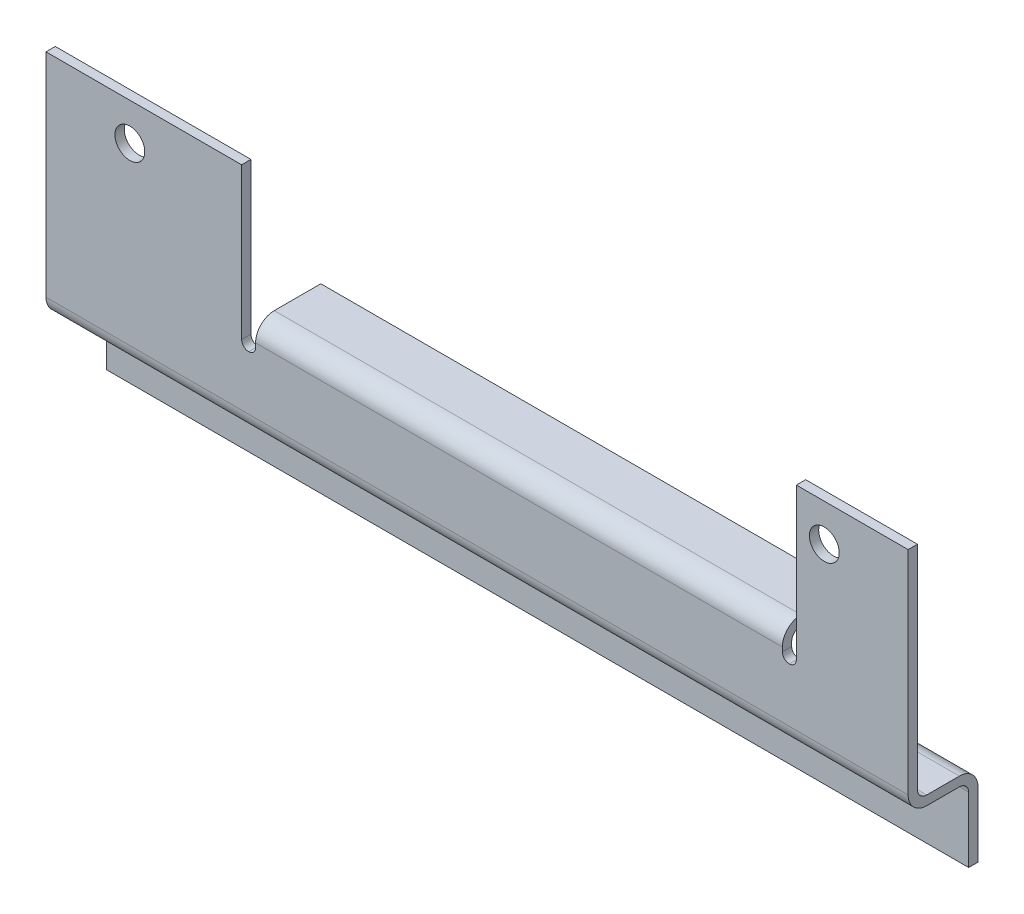
SolidWorks part; units mm, degrees
ref_plane "Face" through (0, 0, 0) normal (0, 0, 1) x (1, 0, 0)
ref_plane "Dessus" through (0, 0, 0) normal (0, 1, 0) x (1, 0, 0)
ref_plane "Droite" through (0, 0, 0) normal (1, 0, 0) x (0, 0, -1)
sketch "Esquisse1" plane through (0, 0, 0) normal (0, 0, 1) x (1, 0, 0)
  line L0 (-46.275, -25.41) -> (-25.275, -25.41)
  line L1 (46.275, -25.41) -> (46.275, -49.22)
  line L3 (-46.275, -25.41) -> (-46.275, -49.22)
  line L5 (34.275, -25.41) -> (34.275, -39.22)
  line L6 (-25.275, -25.41) -> (-25.275, -39.22)
  line L7 (34.275, -25.41) -> (46.275, -25.41)
  line L8 (-25.275, -39.22) -> (34.275, -39.22)
  line L9 (-46.275, -38.22) -> (46.275, -38.22) construction
  line L10 (-46.275, -49.22) -> (46.275, -49.22)
  circle A0 centre (37.275, -29.41) radius 1.75 construction
  circle A1 centre (37.275, -29.41) radius 1.6
  circle A2 centre (-37.275, -29.41) radius 1.6
  dimension "D1" = 4
  dimension "D2" = 12
  dimension "D3" = 21
  dimension "D4" = 1
  dimension "D5" = 10
extrude "Extrusion1" add sketch "Esquisse1" along normal blind 1
sketch "Esquisse2" plane through (0, 0, 1) normal (0, 0, 1) x (1, 0, 0)
  line L1 (-25.275, -39.22) -> (34.275, -39.22)
  line L2 (-25.275, -39.22) -> (-25.275, -40.22)
  line L3 (-25.275, -40.22) -> (34.275, -40.22)
  line L4 (34.275, -39.22) -> (34.275, -40.22)
  dimension "D1" = 1
extrude "Extrusion2" add sketch "Esquisse2" against normal blind 7
sketch "Esquisse3" plane through (0, 0, 1) normal (0, 0, 1) x (1, 0, 0)
  line L1 (-46.275, -49.22) -> (46.275, -49.22)
  line L2 (-46.275, -49.22) -> (-46.275, -50.22)
  line L3 (-46.275, -50.22) -> (46.275, -50.22)
  line L4 (46.275, -49.22) -> (46.275, -50.22)
  dimension "D1" = 1
extrude "Extrusion3" add sketch "Esquisse3" against normal blind 7.5
sketch "Esquisse4" plane through (0, -50.22, 0) normal (0, -1, 0) x (1, 0, 0)
  line L0 (46.275, -6.5) -> (46.275, 1) construction
  line L1 (-46.275, -6.5) -> (46.275, -6.5)
  line L2 (-46.275, -6.5) -> (-46.275, -5.5)
  line L3 (-46.275, -5.5) -> (46.275, -5.5)
  line L4 (46.275, -6.5) -> (46.275, -5.5)
  dimension "D1" = 1
extrude "Extrusion4" add sketch "Esquisse4" along normal blind 8
fillet "Congé1" radius 1 2 edges
fillet "Congé2" radius 2 2 edges at (0, -49.22, -6.5) (0, -50.22, 1)
fillet "Congé3" radius 1 1 edges at (4.5, -40.22, 0)
fillet "Congé4" radius 2 1 edges at (4.5, -39.22, 1)
sketch "Esquisse5" plane through (0, 0, 1) normal (0, 0, 1) x (1, 0, 0)
  line L0 (-25.275, -25.41) -> (-25.275, -42.41)
  line L1 (34.275, -25.41) -> (34.275, -42.41)
  line L2 (-23.775, -25.41) -> (-23.775, -42.41)
  line L3 (32.775, -25.41) -> (32.775, -42.41)
  line L4 (-25.275, -42.41) -> (-23.775, -42.41)
  line L5 (32.775, -42.41) -> (34.275, -42.41)
  line L6 (-25.275, -25.41) -> (-23.775, -25.41)
  line L7 (32.775, -25.41) -> (34.275, -25.41)
  dimension "D1" = 1.5
  dimension "D2" = 1.5
extrude "Enlèv. mat.-Extru.1" cut sketch "Esquisse5" against normal blind 10
fillet "Congé5" radius 0.75 1 edges at (-25.275, -42.41, 0.5)
fillet "Congé6" radius 0.74 1 edges at (-23.775, -42.41, 0.5)
fillet "Congé7" radius 0.74 1 edges at (32.775, -42.41, 0.5)
fillet "Congé8" radius 0.75 1 edges at (34.275, -42.41, 0.5)
